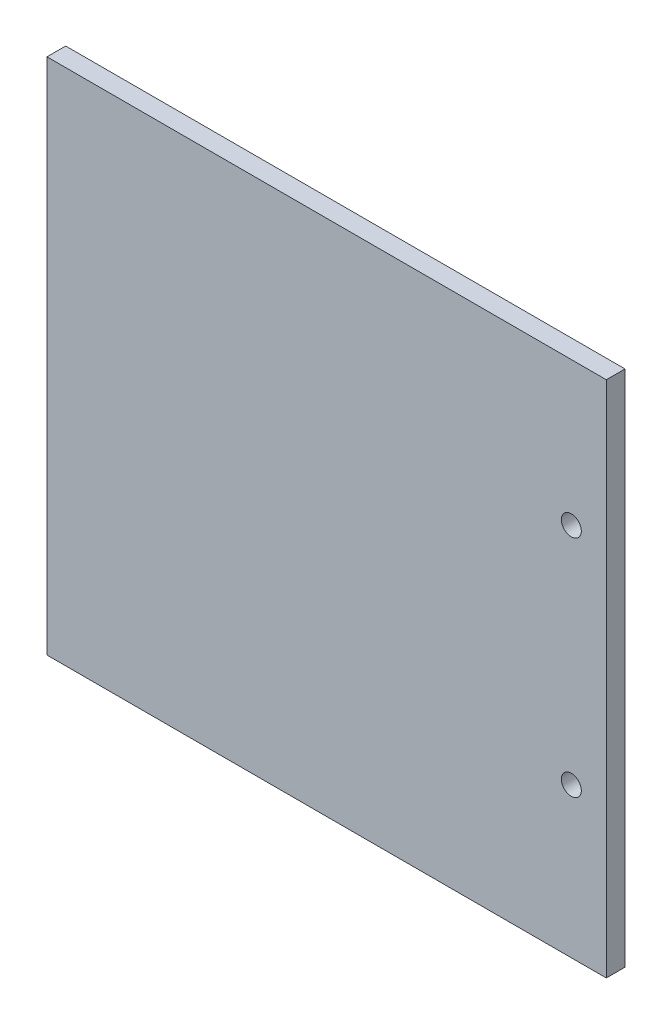
SolidWorks part; units mm, degrees
ref_plane "Front Plane" through (0, 0, 0) normal (0, 0, 1) x (1, 0, 0)
ref_plane "Top Plane" through (0, 0, 0) normal (0, 1, 0) x (1, 0, 0)
ref_plane "Right Plane" through (0, 0, 0) normal (1, 0, 0) x (0, 0, -1)
sketch "Sketch1" plane through (0, 0, 0) normal (0, 0, 1) x (1, 0, 0)
  line L0 (133.35, 0) -> (133.35, 131.7625) construction
  line L1 (0, 0) -> (142.24, 0)
  line L2 (0, 0) -> (0, 131.7625)
  line L3 (0, 131.7625) -> (142.24, 131.7625)
  line L4 (142.24, 0) -> (142.24, 131.7625)
  circle A0 centre (133.35, 38.1) radius 2.54
  circle A1 centre (133.35, 95.25) radius 2.54
extrude "Boss-Extrude1" add sketch "Sketch1" along normal blind 4.7625
